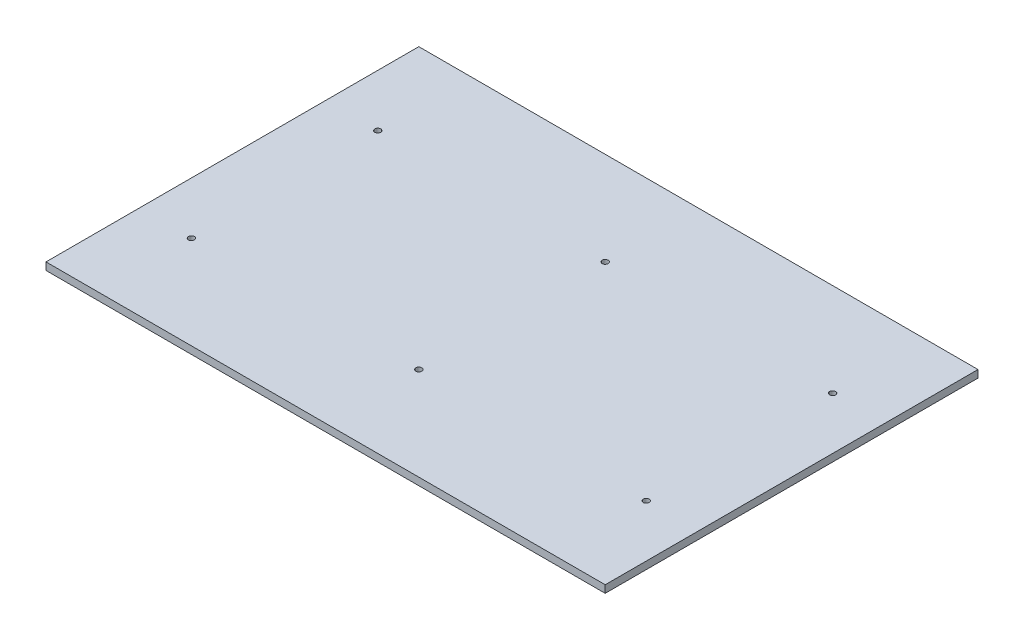
SolidWorks part; units mm, degrees
material "Stainless Steel (ferritic)"
ref_plane "Front Plane" through (0, 0, 0) normal (0, 0, 1) x (1, 0, 0)
ref_plane "Top Plane" through (0, 0, 0) normal (0, 1, 0) x (1, 0, 0)
ref_plane "Right Plane" through (0, 0, 0) normal (1, 0, 0) x (0, 0, -1)
sketch "Sketch1" plane through (0, 0, 0) normal (0, 1, 0) x (1, 0, 0)
  line L1 (-375, 250) -> (375, 250)
  line L2 (-375, 250) -> (-375, -250)
  line L3 (-375, -250) -> (375, -250)
  line L4 (375, 250) -> (375, -250)
  line L5 (-375, 250) -> (375, -250) construction
  line L6 (-375, -250) -> (375, 250) construction
  point P0 (0, 0)
extrude "Boss-Extrude1" add sketch "Sketch1" along normal blind 10
sketch "Sketch2" plane through (0, 10, 0) normal (0, 1, 0) x (1, 0, 0)
  line L0 (375, 250) -> (-375, 250) construction
  line L1 (375, -250) -> (375, 250) construction
  circle A0 centre (305, 125) radius 4
  dimension "D1" = 125
  dimension "D2" = 70
  dimension "D3" = 8
extrude "Cut-Extrude1" cut sketch "Sketch2" against normal blind 10
sketch "Sketch3" plane through (0, 10, 0) normal (0, 1, 0) x (1, 0, 0)
  line L0 (-375, -250) -> (375, -250) construction
  line L1 (375, -250) -> (375, 250) construction
  circle A0 centre (305, -125) radius 4
  dimension "D1" = 125
  dimension "D2" = 70
  dimension "D3" = 8
extrude "Cut-Extrude2" cut sketch "Sketch3" against normal blind 10
sketch "Sketch4" plane through (0, 10, 0) normal (0, 1, 0) x (1, 0, 0)
  line L0 (375, -250) -> (375, 250) construction
  line L1 (375, 250) -> (-375, 250) construction
  circle A0 centre (0, 125) radius 4
  dimension "D1" = 8
  dimension "D2" = 375
  dimension "D3" = 125
extrude "Cut-Extrude3" cut sketch "Sketch4" against normal blind 10
sketch "Sketch5" plane through (0, 10, 0) normal (0, 1, 0) x (1, 0, 0)
  circle A0 centre (0, -125) radius 4
extrude "Cut-Extrude4" cut sketch "Sketch5" against normal blind 10
sketch "Sketch6" plane through (0, 10, 0) normal (0, 1, 0) x (1, 0, 0)
  line L0 (-375, 250) -> (-375, -250) construction
  line L1 (375, 250) -> (-375, 250) construction
  circle A0 centre (-305, 125) radius 4
  dimension "D1" = 70
  dimension "D2" = 125
  dimension "D3" = 8
extrude "Cut-Extrude5" cut sketch "Sketch6" against normal blind 10
sketch "Sketch7" plane through (0, 10, 0) normal (0, 1, 0) x (1, 0, 0)
  line L0 (-375, 250) -> (-375, -250) construction
  line L1 (-375, -250) -> (375, -250) construction
  circle A0 centre (-305, -125) radius 4
  dimension "D1" = 8
  dimension "D2" = 70
  dimension "D3" = 125
extrude "Cut-Extrude6" cut sketch "Sketch7" against normal blind 10 contours A0
sketch "Sketch9" plane through (0, 10, 0) normal (0, 1, 0) x (1, 0, 0)
  line L0 (-375, 250) -> (0, 250) construction
  line L1 (375, 250) -> (-375, 250) construction
  line L2 (-187.5, 250) -> (-187.5, -250) construction
  line L3 (-375, -250) -> (375, -250) construction
